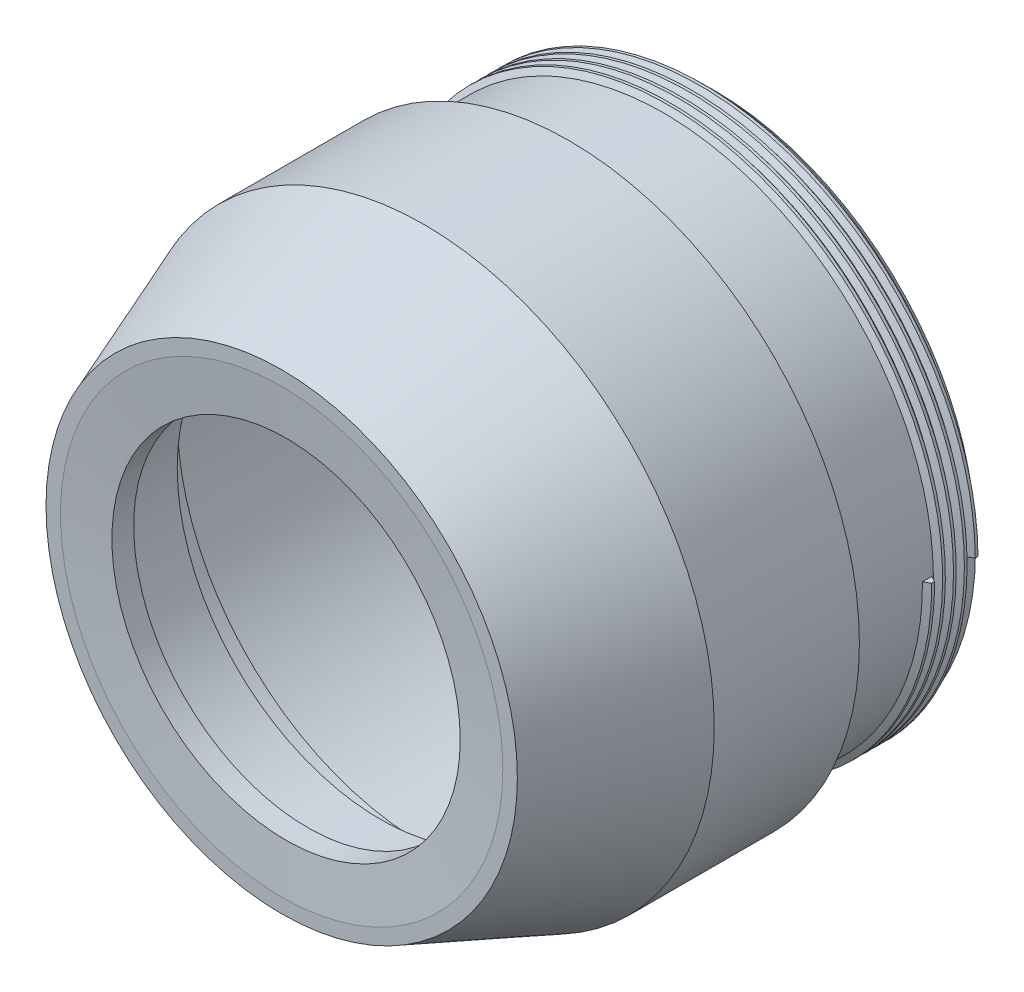
SolidWorks part; units mm, degrees
ref_plane "Ön Düzlem" through (0, 0, 0) normal (0, 0, 1) x (1, 0, 0)
ref_plane "Üst Düzlem" through (0, 0, 0) normal (0, 1, 0) x (1, 0, 0)
ref_plane "Sağ Düzlem" through (0, 0, 0) normal (1, 0, 0) x (0, 0, -1)
sketch "Çizim1" plane through (0, 0, 0) normal (0, 0, 1) x (1, 0, 0)
  circle A0 centre (0, 0) radius 40
  circle A1 centre (0, 0) radius 35
  dimension "D1" = 80
  dimension "D2" = 70
extrude "Yükseklik-Ekstrüzyon1" add sketch "Çizim1" along normal blind 20
ref_plane "Düzlem2" through (0, 0, 20) normal (0, 0, 1) x (1, 0, 0)
sketch "Çizim4" plane through (0, 0, 0) normal (1, 0, 0) x (0, 0, -1)
  line L0 (-20, 34) -> (-20, 40)
  line L1 (-20, 44) -> (-20, -44) construction
  line L4 (-20, 34) -> (-26, 34)
  line L5 (-26, 34) -> (-26, 28)
  line L6 (-26, 28) -> (-36, 28)
  line L7 (-36, 28) -> (-36, 24)
  line L8 (-20, 40) -> (-39.6052, 32.4743)
  line L9 (-36, 24) -> (-39, 24)
  line L10 (-39.6052, 32.4743) -> (-39.6052, 30.4743)
  line L11 (-39.6052, 30.4743) -> (-39, 24)
  point P0 (-31, 28)
  dimension "D1" = 6
  dimension "D2" = 21
  dimension "D3" = 4
  dimension "D4" = 10
  dimension "D5" = 6
ref_axis "Eksen1" through (0, 0, 51.387) along (0, 0, -1)
sketch "Çizim14" plane through (-26.9223, 24.1786, 0) normal (0, 0, -1) x (-1, 0, 0)
  circle A1 centre (-26.9223, -24.1786) radius 37
  circle A2 centre (-26.9223, -24.1786) radius 35
extrude "Yükseklik-Ekstrüzyon6" add sketch "Çizim14" along normal blind 20
chamfer "Pah7" distance 1 angle 45 1 edges at (-37, 0, -20)
chamfer "Pah8" distance 1 angle 45 1 edges at (37, 0, 0)
thread "Diş1" pitch 1.5 method extrude profile "Diş Profili1" start angle 0, offset 0, length 6, pitch 1.5, diameter 74
ref_plane "Düzlem3" through (37, 0, -19) normal (0, 1, 0) x (-1, 0, 0)
sketch "Diş Profili1" plane through (37, 0, -19) normal (0, 1, 0) x (-1, 0, 0)
  line L0 (0, 0) -> (0, 1.5) construction
  line L11 (0, 0) -> (0, 1.3125)
  line L12 (0, 1.3125) -> (-0.8119, 0.8437)
  line L13 (-0.8119, 0.8437) -> (-0.8119, 0.4687)
  line L15 (-0.8119, 0.4687) -> (0, 0)
  line L17 (-0.8119, 0.6562) -> (0, 0.6562) construction
  point P2 (0, 0)
  dimension "Pitch" = 1.5
  dimension "Profile_Angle" = 60
  dimension "Profile_Land" = 0.375
  dimension "Profile_Height" = 0.8119
revolve "Döndür2" add sketch "Çizim4" angle 360 about axis through (0, 0, 51.387) along (0, 0, -1)
